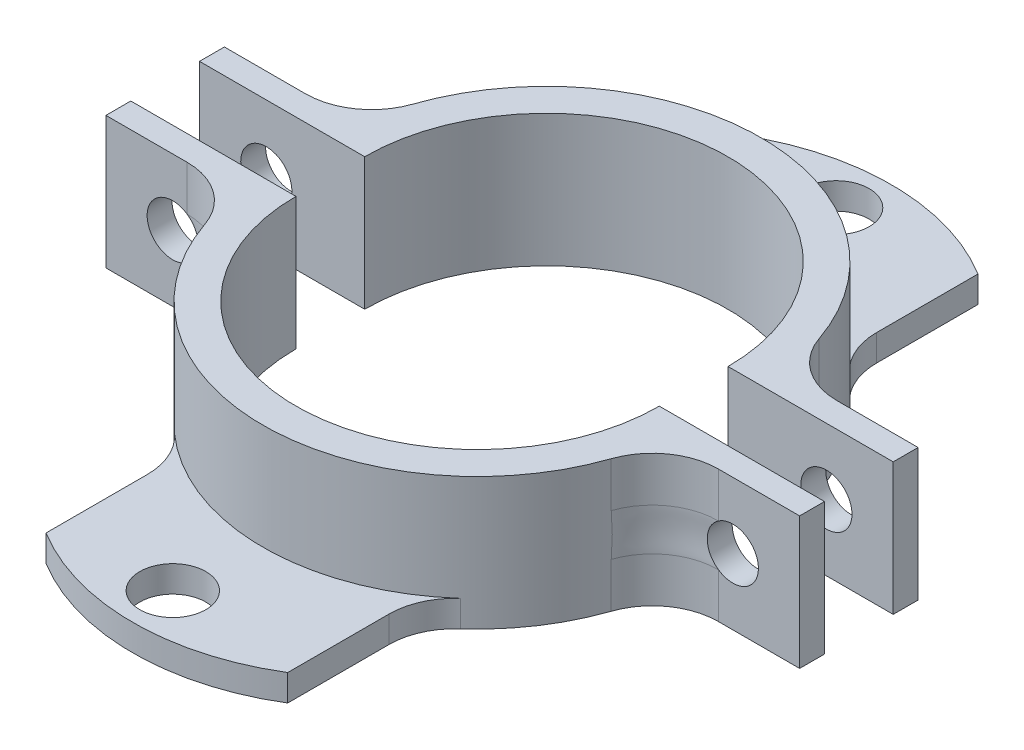
SolidWorks part; units mm, degrees
note: The reader was unsure of these and kept them because the rebuilt part matched: shared geometry of "Sketch1<8>".
material "6061 Alloy"
ref_plane "Front Plane" through (0, 0, 0) normal (0, 0, 1) x (1, 0, 0)
ref_plane "Top Plane" through (0, 0, 0) normal (0, 1, 0) x (1, 0, 0)
ref_plane "Right Plane" through (0, 0, 0) normal (1, 0, 0) x (0, 0, -1)
sketch "Sketch1" plane through (0, 0, 0) normal (0, 1, 0) x (1, 0, 0)
  line L0 (-20.6375, 0) -> (-17.4625, 0)
  line L1 (17.4625, 0) -> (20.6375, 0)
  line L2 (20.6375, 0) -> (33.3375, 0)
  line L3 (33.3375, 0) -> (33.3375, 2.3916)
  line L4 (-11.6154, 29.8712) -> (-11.6154, 17.0584)
  line L5 (11.6154, 29.8712) -> (11.6154, 17.0584)
  line L6 (33.3375, 2.3916) -> (20.4985, 2.3916)
  line L7 (33.3375, 0) -> (20.6375, 0)
  line L8 (0, 0) -> (0, -13.251) construction
  line L9 (-20.6375, 0) -> (-33.3375, 0)
  line L10 (-33.3375, 0) -> (-33.3375, 2.3916)
  line L11 (-33.3375, 2.3916) -> (-20.4985, 2.3916)
  arc A0 (20.6375, 0) -> (-20.6375, 0) centre (0, 0) ccw
  arc A1 (17.4625, 0) -> (-17.4625, 0) centre (0, 0) ccw
  arc A2 (11.6154, 29.8712) -> (-11.6154, 29.8712) centre (0, 10.923) ccw
  circle A3 centre (-0.7251, 28.575) radius 3.175
  dimension "D1" = 28.575
  dimension "D2" = 3.175
  dimension "D3" = 12.7
  dimension "D5" = 6.35
  dimension "D4" = 2.3916
extrude "Boss-Extrude3" add sketch "Sketch1" along normal blind 12.7 contours A1 L1 A0 L0 | A0 L2 L3 L6 | A0 L11 L10 L9
extrude "Boss-Extrude4" add sketch "Sketch1<8>" along normal blind 2.54 contours L5 A2 L4 A0 A3
sketch "Sketch1<8>" plane through (0, 0, 0) normal (0, 1, 0) x (1, 0, 0) same geometry as "Sketch1"
hole_wizard "#10 (0.1935) Diameter Hole1" positions "Sketch4" profile "Sketch5" hole size "#10" standard "ANSI Inch" end condition up to next
sketch "Sketch4" plane through (0, 0, -2.3916) normal (0, 0, -1) x (-1, 0, 0)
  line L0 (-33.3375, 0) -> (-20.4985, 12.7) construction
  line L3 (20.4985, 12.7) -> (33.3375, 0) construction
  line L4 (33.3375, 0) -> (20.4985, 0) construction
  point P0 (-26.918, 6.35)
  point P2 (26.918, 6.35)
  point P23 (26.918, 6.35)
  point P25 (-26.918, 6.35)
sketch "Sketch5" plane through (26.918, 6.35, -2.3916) normal (1, 0, 0) x (0, 1, 0)
  line L0 (0, 0) -> (0, 2.3916)
  line L1 (0, 2.3916) -> (2.4574, 2.3916)
  line L2 (2.4574, 2.3916) -> (2.4574, 0)
  line L5 (2.4574, 0) -> (0, 0)
  line L11 (0, -6.35) -> (0, 107.95) construction
  dimension "Thru Hole Dia." = 4.9149
  dimension "Thru Hole Depth" = 2.3916
ref_plane "Plane1" through (0, 0, 3.302) normal (0, 0, 1) x (1, 0, 0)
fillet "Fillet1" radius 6.35 4 edges at (20.4985, 6.35, -2.3916) (11.6154, 1.27, -17.0584) (-11.6154, 1.27, -17.0584) (-20.4985, 6.35, -2.3916)
mirror "Mirror3" about plane through (0, 0, 3.302) normal (0, 0, 1) of bodies 105
